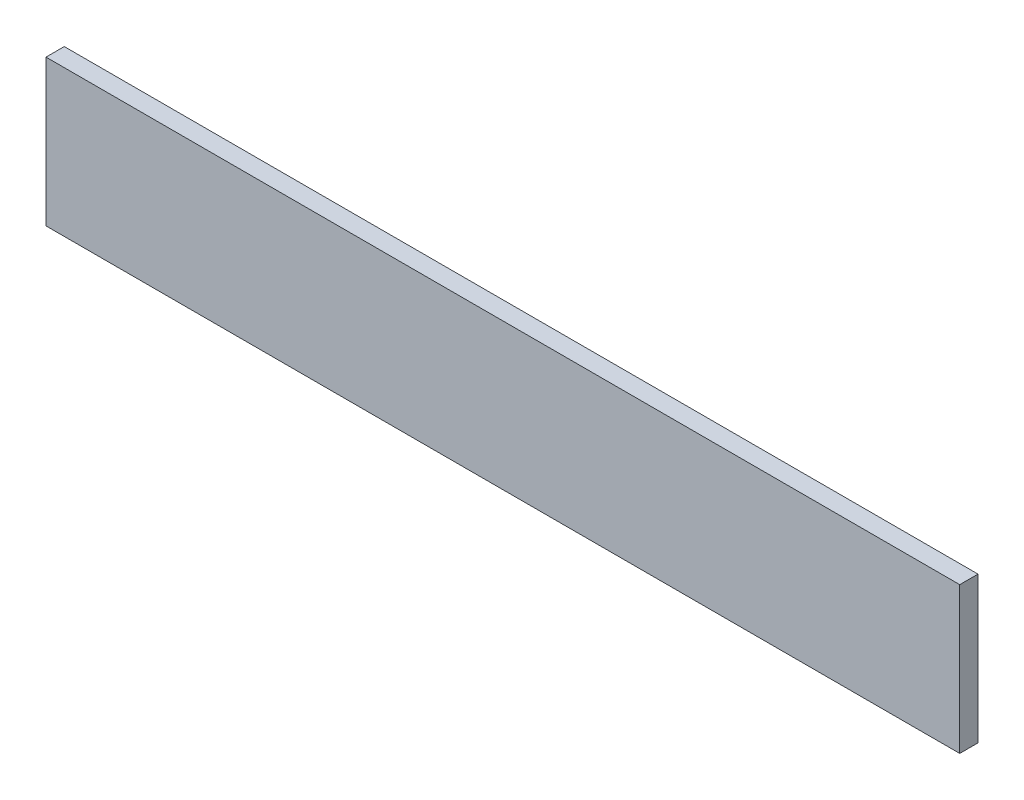
SolidWorks part; units mm, degrees
material "Pine"
ref_plane "Front Plane" through (0, 0, 0) normal (0, 0, 1) x (1, 0, 0)
ref_plane "Top Plane" through (0, 0, 0) normal (0, 1, 0) x (1, 0, 0)
ref_plane "Right Plane" through (0, 0, 0) normal (1, 0, 0) x (0, 0, -1)
sketch "Sketch1" plane through (0, 0, 0) normal (0, 0, 1) x (1, 0, 0)
  line L1 (-250, -40) -> (250, -40)
  line L2 (-250, -40) -> (-250, 40)
  line L3 (-250, 40) -> (250, 40)
  line L4 (250, -40) -> (250, 40)
  line L5 (-250, -40) -> (250, 40) construction
  line L6 (-250, 40) -> (250, -40) construction
  point P0 (0, 0)
  dimension "D1" = 500
  dimension "D2" = 80
extrude "Boss-Extrude1" add sketch "Sketch1" along normal blind 10
sketch "Sketch3" plane through (0, 0, 10) normal (0, 0, 1) x (1, 0, 0)
  line L0 (-250, 0) -> (250, 0) construction
  line L1 (-250, 40) -> (-250, -40) construction
  line L2 (250, -40) -> (250, 40) construction
  line L3 (0, 40) -> (0, -40) construction
  line L4 (250, 40) -> (-250, 40) construction
  line L5 (-250, -40) -> (250, -40) construction
  circle A0 centre (0, 0) radius 4
  circle A2 centre (-140, 0) radius 4
  circle A5 centre (140, 0) radius 4
  dimension "D1" = 8
  dimension "D3" = 8
  dimension "D6" = 140
